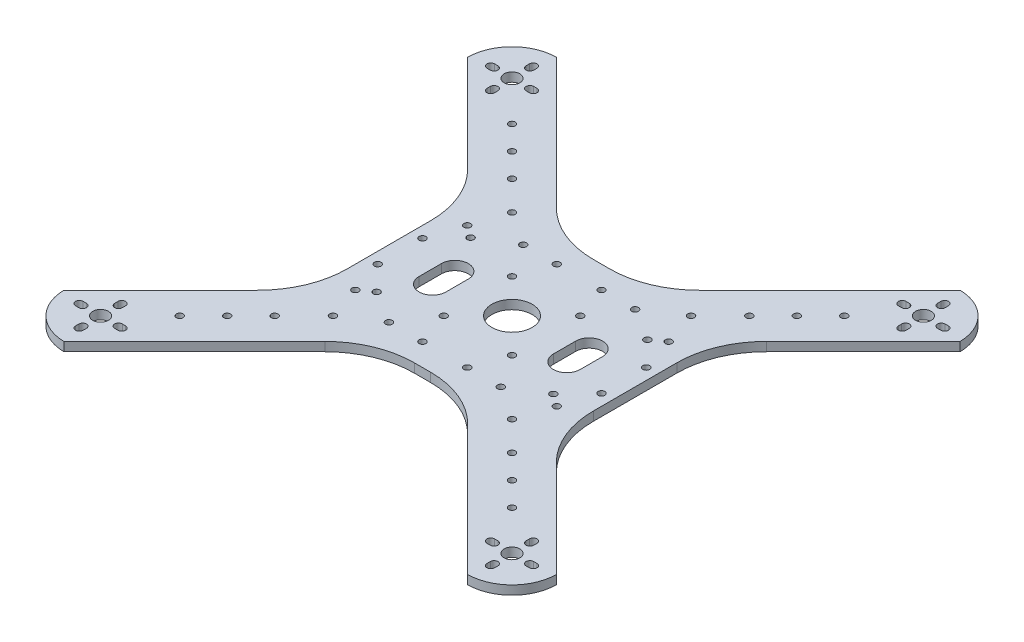
SolidWorks part; units mm, degrees
material "Thornel Mat VMA"
ref_plane "前视基准面" through (0, 0, 0) normal (0, 0, 1) x (1, 0, 0)
ref_plane "上视基准面" through (0, 0, 0) normal (0, 1, 0) x (1, 0, 0)
ref_plane "右视基准面" through (0, 0, 0) normal (1, 0, 0) x (0, 0, -1)
other "Configuration Table"
sketch "草图1" plane through (0, 0, 0) normal (0, 1, 0) x (1, 0, 0)
  line L9 (-110, -110) -> (110, -110)
  line L10 (-110, -110) -> (-110, 110)
  line L11 (-110, 110) -> (110, 110)
  line L12 (110, -110) -> (110, 110)
  line L13 (0, 110) -> (0, -110) construction
  line L14 (-110, 0) -> (110, 0) construction
  point P0 (0, 0)
  dimension "D1" = 220
  dimension "D2" = 220
extrude "凸台-拉伸1" add sketch "草图1" along normal blind 4
sketch "草图2" plane through (0, 4, 0) normal (0, 1, 0) x (1, 0, 0)
  line L0 (-91.9239, 91.9239) -> (0, 0) construction
  line L1 (0, -1000) -> (0, 49000) construction
  line L2 (-91.9239, 99.9239) -> (-91.9239, 101.4239) construction
  line L3 (-93.6239, 99.9239) -> (-93.6239, 101.4239)
  line L4 (-90.2239, 99.9239) -> (-90.2239, 101.4239)
  line L5 (-83.9239, 90.2239) -> (-82.4239, 90.2239)
  line L6 (-83.9239, 93.6239) -> (-82.4239, 93.6239)
  line L7 (-83.9239, 91.9239) -> (-82.4239, 91.9239) construction
  line L8 (-93.6239, 83.9239) -> (-93.6239, 82.4239)
  line L9 (-90.2239, 83.9239) -> (-90.2239, 82.4239)
  line L10 (-91.9239, 83.9239) -> (-91.9239, 82.4239) construction
  line L11 (-99.9239, 93.6239) -> (-101.4239, 93.6239)
  line L12 (-99.9239, 90.2239) -> (-101.4239, 90.2239)
  line L13 (-99.9239, 91.9239) -> (-101.4239, 91.9239) construction
  line L14 (99.9239, 91.9239) -> (101.4239, 91.9239) construction
  line L15 (99.9239, 93.6239) -> (101.4239, 93.6239)
  line L16 (99.9239, 90.2239) -> (101.4239, 90.2239)
  line L17 (91.9239, 83.9239) -> (91.9239, 82.4239) construction
  line L18 (93.6239, 83.9239) -> (93.6239, 82.4239)
  line L19 (90.2239, 83.9239) -> (90.2239, 82.4239)
  line L20 (83.9239, 91.9239) -> (82.4239, 91.9239) construction
  line L21 (83.9239, 90.2239) -> (82.4239, 90.2239)
  line L22 (83.9239, 93.6239) -> (82.4239, 93.6239)
  line L23 (91.9239, 99.9239) -> (91.9239, 101.4239) construction
  line L24 (90.2239, 99.9239) -> (90.2239, 101.4239)
  line L25 (93.6239, 99.9239) -> (93.6239, 101.4239)
  line L26 (91.9239, -99.9239) -> (91.9239, -101.4239) construction
  line L27 (93.6239, -99.9239) -> (93.6239, -101.4239)
  line L28 (90.2239, -99.9239) -> (90.2239, -101.4239)
  line L29 (83.9239, -91.9239) -> (82.4239, -91.9239) construction
  line L30 (83.9239, -93.6239) -> (82.4239, -93.6239)
  line L31 (83.9239, -90.2239) -> (82.4239, -90.2239)
  line L32 (91.9239, -83.9239) -> (91.9239, -82.4239) construction
  line L33 (90.2239, -83.9239) -> (90.2239, -82.4239)
  line L34 (93.6239, -83.9239) -> (93.6239, -82.4239)
  line L35 (99.9239, -91.9239) -> (101.4239, -91.9239) construction
  line L36 (99.9239, -90.2239) -> (101.4239, -90.2239)
  line L37 (99.9239, -93.6239) -> (101.4239, -93.6239)
  line L38 (-99.9239, -91.9239) -> (-101.4239, -91.9239) construction
  line L39 (-99.9239, -93.6239) -> (-101.4239, -93.6239)
  line L40 (-99.9239, -90.2239) -> (-101.4239, -90.2239)
  line L41 (-91.9239, -83.9239) -> (-91.9239, -82.4239) construction
  line L42 (-93.6239, -83.9239) -> (-93.6239, -82.4239)
  line L43 (-90.2239, -83.9239) -> (-90.2239, -82.4239)
  line L44 (-83.9239, -91.9239) -> (-82.4239, -91.9239) construction
  line L45 (-83.9239, -90.2239) -> (-82.4239, -90.2239)
  line L46 (-83.9239, -93.6239) -> (-82.4239, -93.6239)
  line L47 (-91.9239, -99.9239) -> (-91.9239, -101.4239) construction
  line L48 (-90.2239, -99.9239) -> (-90.2239, -101.4239)
  line L49 (-93.6239, -99.9239) -> (-93.6239, -101.4239)
  circle A0 centre (-91.9239, 91.9239) radius 3.5
  arc A8 (-93.6239, 99.9239) -> (-90.2239, 99.9239) centre (-91.9239, 99.9239) ccw
  arc A9 (-90.2239, 101.4239) -> (-93.6239, 101.4239) centre (-91.9239, 101.4239) ccw
  arc A10 (-83.9239, 93.6239) -> (-83.9239, 90.2239) centre (-83.9239, 91.9239) ccw
  arc A11 (-82.4239, 90.2239) -> (-82.4239, 93.6239) centre (-82.4239, 91.9239) ccw
  arc A12 (-90.2239, 83.9239) -> (-93.6239, 83.9239) centre (-91.9239, 83.9239) ccw
  arc A13 (-93.6239, 82.4239) -> (-90.2239, 82.4239) centre (-91.9239, 82.4239) ccw
  arc A14 (-99.9239, 90.2239) -> (-99.9239, 93.6239) centre (-99.9239, 91.9239) ccw
  arc A15 (-101.4239, 93.6239) -> (-101.4239, 90.2239) centre (-101.4239, 91.9239) ccw
  circle A16 centre (91.9239, 91.9239) radius 3.5
  arc A17 (99.9239, 93.6239) -> (99.9239, 90.2239) centre (99.9239, 91.9239) ccw
  arc A18 (101.4239, 90.2239) -> (101.4239, 93.6239) centre (101.4239, 91.9239) ccw
  arc A19 (93.6239, 83.9239) -> (90.2239, 83.9239) centre (91.9239, 83.9239) ccw
  arc A20 (90.2239, 82.4239) -> (93.6239, 82.4239) centre (91.9239, 82.4239) ccw
  arc A21 (83.9239, 90.2239) -> (83.9239, 93.6239) centre (83.9239, 91.9239) ccw
  arc A22 (82.4239, 93.6239) -> (82.4239, 90.2239) centre (82.4239, 91.9239) ccw
  arc A23 (90.2239, 99.9239) -> (93.6239, 99.9239) centre (91.9239, 99.9239) ccw
  arc A24 (93.6239, 101.4239) -> (90.2239, 101.4239) centre (91.9239, 101.4239) ccw
  circle A25 centre (91.9239, -91.9239) radius 3.5
  arc A26 (93.6239, -99.9239) -> (90.2239, -99.9239) centre (91.9239, -99.9239) ccw
  arc A27 (90.2239, -101.4239) -> (93.6239, -101.4239) centre (91.9239, -101.4239) ccw
  arc A28 (83.9239, -93.6239) -> (83.9239, -90.2239) centre (83.9239, -91.9239) ccw
  arc A29 (82.4239, -90.2239) -> (82.4239, -93.6239) centre (82.4239, -91.9239) ccw
  arc A30 (90.2239, -83.9239) -> (93.6239, -83.9239) centre (91.9239, -83.9239) ccw
  arc A31 (93.6239, -82.4239) -> (90.2239, -82.4239) centre (91.9239, -82.4239) ccw
  arc A32 (99.9239, -90.2239) -> (99.9239, -93.6239) centre (99.9239, -91.9239) ccw
  arc A33 (101.4239, -93.6239) -> (101.4239, -90.2239) centre (101.4239, -91.9239) ccw
  circle A34 centre (-91.9239, -91.9239) radius 3.5
  arc A35 (-99.9239, -93.6239) -> (-99.9239, -90.2239) centre (-99.9239, -91.9239) ccw
  arc A36 (-101.4239, -90.2239) -> (-101.4239, -93.6239) centre (-101.4239, -91.9239) ccw
  arc A37 (-93.6239, -83.9239) -> (-90.2239, -83.9239) centre (-91.9239, -83.9239) ccw
  arc A38 (-90.2239, -82.4239) -> (-93.6239, -82.4239) centre (-91.9239, -82.4239) ccw
  arc A39 (-83.9239, -90.2239) -> (-83.9239, -93.6239) centre (-83.9239, -91.9239) ccw
  arc A40 (-82.4239, -93.6239) -> (-82.4239, -90.2239) centre (-82.4239, -91.9239) ccw
  arc A41 (-90.2239, -99.9239) -> (-93.6239, -99.9239) centre (-91.9239, -99.9239) ccw
  arc A42 (-93.6239, -101.4239) -> (-90.2239, -101.4239) centre (-91.9239, -101.4239) ccw
  point P10 (-91.9239, 100.6739)
  point P17 (0, 0)
  point P21 (-83.1739, 91.9239)
  point P26 (0, 0)
  point P29 (-91.9239, 83.1739)
  point P36 (-100.6739, 91.9239)
  point P41 (-91.9239, 91.9239)
  point P46 (100.6739, 91.9239)
  point P53 (91.9239, 83.1739)
  point P60 (83.1739, 91.9239)
  point P67 (91.9239, 100.6739)
  point P76 (91.9239, -100.6739)
  point P83 (83.1739, -91.9239)
  point P90 (91.9239, -83.1739)
  point P97 (100.6739, -91.9239)
  point P106 (-100.6739, -91.9239)
  point P113 (-91.9239, -83.1739)
  point P120 (-83.1739, -91.9239)
  point P127 (-91.9239, -100.6739)
  point P132 (0, 0)
  dimension "D1" = 7
  dimension "D2" = 130
  dimension "D4" = 1.5
  dimension "D5" = 8
  dimension "D6" = 1.7
  dimension "D3" = 45
  dimension "D7" = 4
extrude "切除-拉伸1 电机" cut sketch "草图2" against normal through all
sketch "草图4" plane through (0, 4, 0) normal (0, 1, 0) x (1, 0, 0)
  line L1 (-15.25, -15.25) -> (15.25, -15.25) construction
  line L2 (-15.25, -15.25) -> (-15.25, 15.25) construction
  line L3 (-15.25, 15.25) -> (15.25, 15.25) construction
  line L4 (15.25, -15.25) -> (15.25, 15.25) construction
  line L5 (0, 15.25) -> (0, -15.25) construction
  line L6 (-15.25, 0) -> (15.25, 0) construction
  circle A0 centre (-15.25, 15.25) radius 1.5
  circle A1 centre (15.25, 15.25) radius 1.5
  circle A2 centre (15.25, -15.25) radius 1.5
  circle A3 centre (-15.25, -15.25) radius 1.5
  point P0 (0, 0)
  point P14 (0, 0)
  dimension "D3" = 3
  dimension "D1" = 30.5
  dimension "D2" = 30.5
extrude "切除-拉伸2 飞塔" cut sketch "草图4" against normal through all
sketch "草图5" plane through (0, 4, 0) normal (0, 1, 0) x (1, 0, 0)
  line L1 (-39.5, -21) -> (39.5, -21) construction
  line L2 (-39.5, -21) -> (-39.5, 21) construction
  line L3 (-39.5, 21) -> (39.5, 21) construction
  line L4 (39.5, -21) -> (39.5, 21) construction
  line L5 (0, 21) -> (0, -21) construction
  line L6 (-39.5, 0) -> (39.5, 0) construction
  circle A0 centre (-39.5, 21) radius 1.5
  circle A1 centre (39.5, 21) radius 1.5
  circle A2 centre (39.5, -21) radius 1.5
  circle A3 centre (-39.5, -21) radius 1.5
  point P0 (0, 0)
  dimension "D3" = 3
  dimension "D4" = 3
  dimension "D5" = 3
  dimension "D6" = 3
  dimension "D1" = 42
  dimension "D2" = 79
extrude "切除-拉伸3 NX载板" cut sketch "草图5" against normal through all
sketch "草图6" plane through (0, 4, 0) normal (0, 1, 0) x (1, 0, 0)
  line L1 (-45, -25) -> (45, -25) construction
  line L2 (-45, -25) -> (-45, 25) construction
  line L3 (-45, 25) -> (45, 25) construction
  line L4 (45, -25) -> (45, 25) construction
  line L5 (0, 25) -> (0, -25) construction
  line L6 (-45, 0) -> (45, 0) construction
  circle A0 centre (-45, 25) radius 1.5
  circle A1 centre (45, 25) radius 1.5
  circle A2 centre (45, -25) radius 1.5
  circle A3 centre (-45, -25) radius 1.5
  point P0 (0, 0)
  dimension "D3" = 3
  dimension "D4" = 3
  dimension "D5" = 3
  dimension "D6" = 3
  dimension "D1" = 50
  dimension "D2" = 90
extrude "切除-拉伸4" cut sketch "草图6" against normal through all
sketch "草图9" plane through (0, 4, 0) normal (0, 1, 0) x (1, 0, 0)
  line L0 (-90.201, 110) -> (-20.201, 40)
  line L1 (110, 110) -> (-110, 110) construction
  line L2 (-20.201, 40) -> (20.201, 40)
  line L3 (20.201, 40) -> (90.201, 110)
  line L4 (90.201, 110) -> (-90.201, 110)
  line L5 (-110, 90.201) -> (-55, 35.201)
  line L6 (-110, 110) -> (-110, -110) construction
  line L7 (-55, 35.201) -> (-55, -35.201)
  line L8 (-55, -35.201) -> (-110, -90.201)
  line L9 (-110, -90.201) -> (-110, 90.201)
  line L10 (-1000, 0) -> (49000, 0) construction
  line L11 (0, -1000) -> (0, 49000) construction
  line L20 (20.201, -40) -> (90.201, -110)
  line L21 (-20.201, -40) -> (20.201, -40)
  line L22 (-90.201, -110) -> (-20.201, -40)
  line L23 (90.201, -110) -> (-90.201, -110)
  line L24 (55, -35.201) -> (110, -90.201)
  line L25 (55, 35.201) -> (55, -35.201)
  line L26 (110, 90.201) -> (55, 35.201)
  line L27 (110, -90.201) -> (110, 90.201)
  circle A3 centre (-91.9239, 91.9239) radius 3.5 construction
  circle A4 centre (91.9239, 91.9239) radius 3.5 construction
  circle A5 centre (-91.9239, -91.9239) radius 3.5 construction
  dimension "D8" = 14
  dimension "D1" = 45
  dimension "D2" = 45
  dimension "D3" = 14
  dimension "D4" = 14
  dimension "D5" = 45
  dimension "D6" = 45
  dimension "D7" = 14
  dimension "D9" = 55
  dimension "D10" = 40
extrude "切除-拉伸5" cut sketch "草图9" against normal through all
fillet "圆角2" radius 40 8 edges at (-55, 2, -35.201) (-55, 2, 35.201) (-20.201, 2, 40) (20.201, 2, 40) (55, 2, 35.201) (55, 2, -35.201) (20.201, 2, -40) (-20.201, 2, -40)
fillet "圆角3" radius 20 4 edges at (-110, 2, 110) (110, 2, 110) (110, 2, -110) (-110, 2, -110)
sketch "草图10" plane through (0, 4, 0) normal (0, 1, 0) x (1, 0, 0)
  line L0 (0, 0) -> (-91.9239, 91.9239) construction
  line L1 (-1000, 0) -> (49000, 0) construction
  line L2 (0, -1000) -> (0, 49000) construction
  circle A3 centre (74.2462, 74.2462) radius 1.5
  circle A4 centre (-63.6396, 63.6396) radius 1.5
  circle A5 centre (-74.2462, 74.2462) radius 1.5
  circle A6 centre (-53.033, 53.033) radius 1.5
  circle A7 centre (-91.9239, 91.9239) radius 3.5 construction
  circle A8 centre (63.6396, 63.6396) radius 1.5
  circle A9 centre (53.033, 53.033) radius 1.5
  circle A10 centre (74.2462, -74.2462) radius 1.5
  circle A11 centre (63.6396, -63.6396) radius 1.5
  circle A12 centre (53.033, -53.033) radius 1.5
  circle A13 centre (-74.2462, -74.2462) radius 1.5
  circle A14 centre (-63.6396, -63.6396) radius 1.5
  circle A15 centre (-53.033, -53.033) radius 1.5
  circle A16 centre (-40, 40) radius 1.5
  circle A17 centre (40, 40) radius 1.5
  circle A18 centre (40, -40) radius 1.5
  circle A19 centre (-40, -40) radius 1.5
  circle A20 centre (-25, 30) radius 1.5
  circle A21 centre (-10, 30) radius 1.5
  circle A22 centre (-10, -30) radius 1.5
  circle A23 centre (-25, -30) radius 1.5
  circle A24 centre (10, -30) radius 1.5
  circle A25 centre (25, -30) radius 1.5
  circle A26 centre (10, 30) radius 1.5
  circle A27 centre (25, 30) radius 1.5
  circle A28 centre (-50, 10) radius 1.5
  circle A29 centre (-50, -10) radius 1.5
  circle A30 centre (50, -10) radius 1.5
  circle A31 centre (50, 10) radius 1.5
  point P33 (0, 0)
  point P42 (0, 0)
  dimension "D1" = 3
  dimension "D2" = 3
  dimension "D3" = 3
  dimension "D4" = 25
  dimension "D5" = 15
  dimension "D6" = 15
  dimension "D7" = 3
  dimension "D8" = 40
  dimension "D9" = 10
  dimension "D10" = 15
  dimension "D11" = 30
  dimension "D12" = 3
  dimension "D13" = 3
  dimension "D14" = 10
  dimension "D15" = 50
  dimension "D16" = 3
extrude "切除-拉伸6" cut sketch "草图10" against normal through all
sketch "草图11" plane through (0, 4, 0) normal (0, 1, 0) x (1, 0, 0)
  line L0 (-30, -5.5212) -> (-30, 4.4788) construction
  line L1 (-36, -5.5212) -> (-36, 4.4788)
  line L2 (-24, -5.5212) -> (-24, 4.4788)
  line L3 (0, -1000) -> (0, 49000) construction
  line L4 (30, -5.5212) -> (30, 4.4788) construction
  line L5 (36, -5.5212) -> (36, 4.4788)
  line L6 (24, -5.5212) -> (24, 4.4788)
  circle A0 centre (0, 0) radius 9
  arc A1 (-36, -5.5212) -> (-24, -5.5212) centre (-30, -5.5212) ccw
  arc A2 (-24, 4.4788) -> (-36, 4.4788) centre (-30, 4.4788) ccw
  arc A3 (36, -5.5212) -> (24, -5.5212) centre (30, -5.5212) cw
  arc A4 (24, 4.4788) -> (36, 4.4788) centre (30, 4.4788) cw
  point P5 (-30, -0.5212)
  point P14 (30, -0.5212)
  dimension "D1" = 18
  dimension "D2" = 6
  dimension "D3" = 10
  dimension "D4" = 60
extrude "切除-拉伸7" cut sketch "草图11" against normal through all
